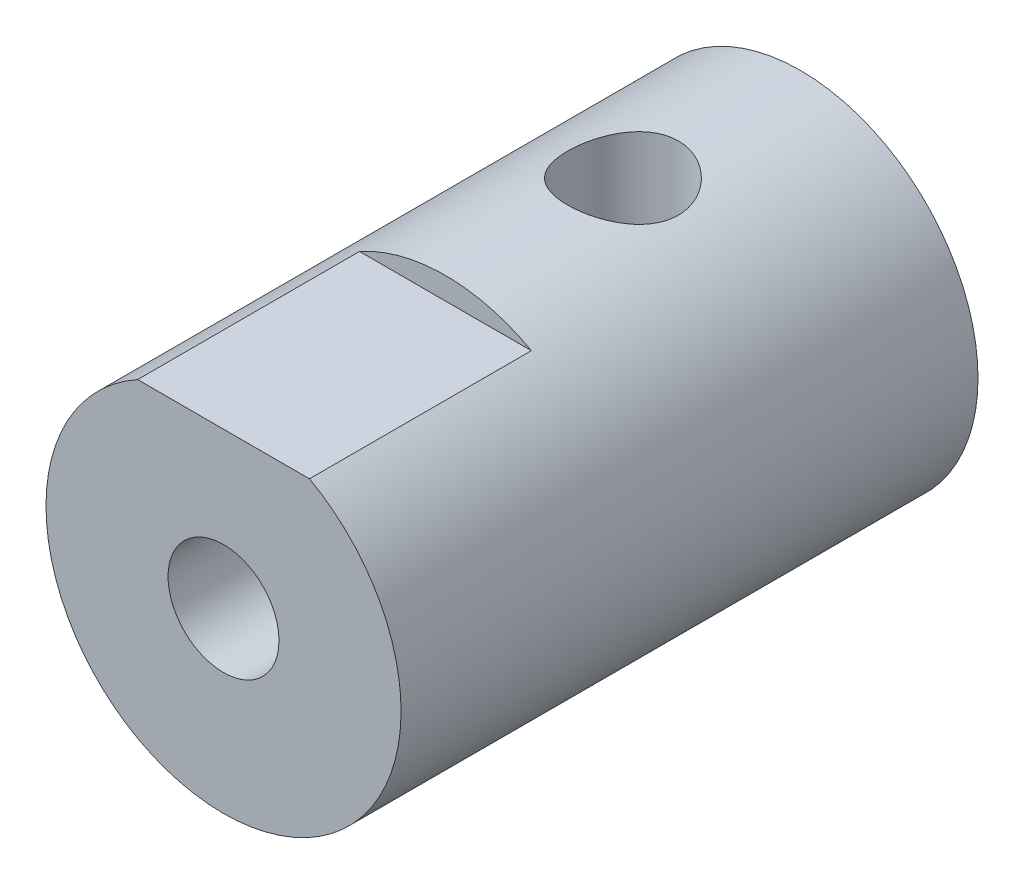
SolidWorks part; units mm, degrees
ref_plane "Front Plane" through (0, 0, 0) normal (0, 0, 1) x (1, 0, 0)
ref_plane "Top Plane" through (0, 0, 0) normal (0, 1, 0) x (1, 0, 0)
ref_plane "Right Plane" through (0, 0, 0) normal (1, 0, 0) x (0, 0, -1)
sketch "Sketch1" plane through (0, 0, 0) normal (0, 0, 1) x (1, 0, 0)
  line L0 (-1.9365, 3.5) -> (1.9365, 3.5)
  arc A0 (-1.9365, 3.5) -> (1.9365, 3.5) centre (0, 0) ccw
  dimension "D1" = 8
  dimension "D2" = 3.5
extrude "Boss-Extrude1" add sketch "Sketch1" along normal blind 5
sketch "Sketch2" plane through (0, 0, 0) normal (0, 0, -1) x (-1, 0, 0)
  circle A0 centre (0, 0) radius 4
  dimension "D1" = 8
extrude "Boss-Extrude2" add sketch "Sketch2" along normal blind 8
sketch "Sketch3" plane through (0, 0, -8) normal (0, 0, -1) x (-1, 0, 0)
  line L0 (-1.3229, 1.5) -> (1.3229, 1.5)
  arc A0 (-1.3229, 1.5) -> (1.3229, 1.5) centre (0, 0) ccw
  dimension "D1" = 4
  dimension "D2" = 1.5
extrude "Cut-Extrude1" cut sketch "Sketch3" against normal blind 8
sketch "Sketch4" plane through (0, 0, 5) normal (0, 0, 1) x (1, 0, 0)
  circle A0 centre (0, 0) radius 1.25
  dimension "D1" = 2.5
extrude "Cut-Extrude2" cut sketch "Sketch4" against normal blind 8
ref_plane "Plane1" through (0, 4, 0) normal (0, 1, 0) x (1, 0, 0)
sketch "Sketch5" plane through (0, 4, 0) normal (0, 1, 0) x (1, 0, 0)
  circle A0 centre (0, 4) radius 1.25
  dimension "D2" = 2.5
  dimension "D1" = 4
extrude "Cut-Extrude3" cut sketch "Sketch5" against normal up to vertex (4 mm away) up to point (0, 0, 0)
